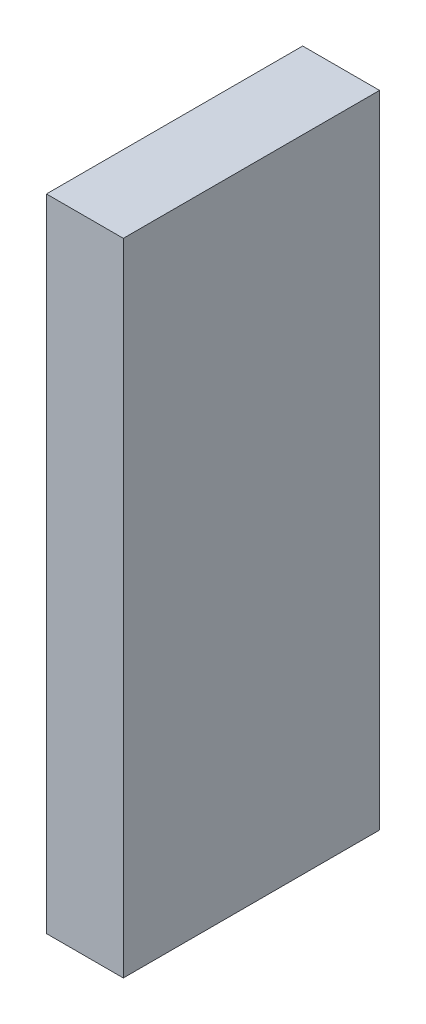
SolidWorks part; units mm, degrees
ref_plane "Front Plane" through (0, 0, 0) normal (0, 0, 1) x (1, 0, 0)
ref_plane "Top Plane" through (0, 0, 0) normal (0, 1, 0) x (1, 0, 0)
ref_plane "Right Plane" through (0, 0, 0) normal (1, 0, 0) x (0, 0, -1)
sketch "Sketch1" plane through (0, 0, 0) normal (0, 1, 0) x (1, 0, 0)
  line L1 (-6, 20) -> (6, 20)
  line L2 (-6, 20) -> (-6, -20)
  line L3 (-6, -20) -> (6, -20)
  line L4 (6, 20) -> (6, -20)
  line L5 (-6, 20) -> (6, -20) construction
  line L6 (-6, -20) -> (6, 20) construction
  point P0 (0, 0)
  dimension "D1" = 40
  dimension "D2" = 12
extrude "Boss-Extrude1" add sketch "Sketch1" along normal mid plane 100
